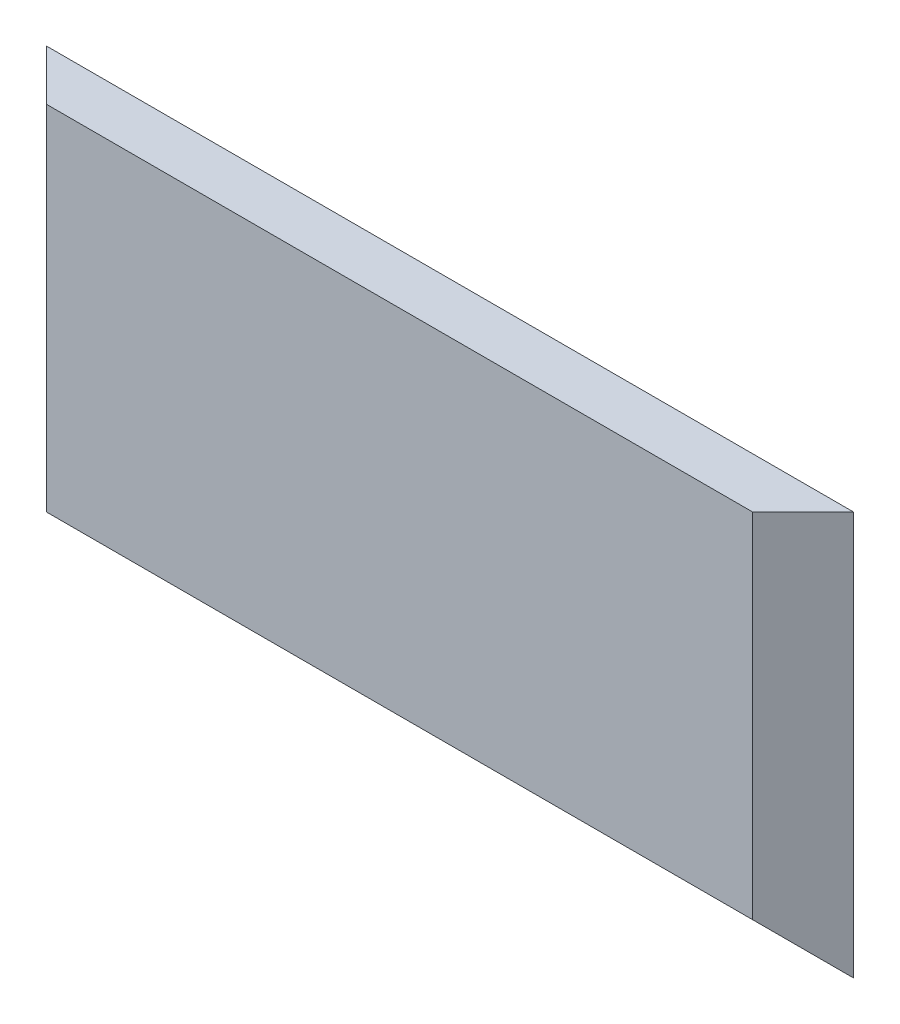
SolidWorks part; units mm, degrees
ref_plane "Front Plane" through (0, 0, 0) normal (0, 0, 1) x (1, 0, 0)
ref_plane "Top Plane" through (0, 0, 0) normal (0, 1, 0) x (1, 0, 0)
ref_plane "Right Plane" through (0, 0, 0) normal (1, 0, 0) x (0, 0, -1)
sketch "Sketch3" plane through (0, 0, 0) normal (0, 1, 0) x (1, 0, 0)
  line L0 (-40, 2.5) -> (-35, -2.5)
  line L1 (-40, 2.5) -> (40, 2.5)
  line L2 (-40, 2.5) -> (-40, -2.5) construction
  line L3 (-35, -2.5) -> (35, -2.5)
  line L4 (40, 2.5) -> (40, -2.5) construction
  line L5 (-40, 2.5) -> (40, -2.5) construction
  line L6 (-40, -2.5) -> (40, 2.5) construction
  line L7 (40, 2.5) -> (35, -2.5)
  point P0 (0, 0)
  dimension "D1" = 5
  dimension "D2" = 80
  dimension "D3" = 45
  dimension "D4" = 45
extrude "Boss-Extrude2" add sketch "Sketch3" along normal blind 40
sketch "Sketch4" plane through (0, 0, 0) normal (1, 0, 0) x (0, 0, -1)
  line L0 (-2.5, 0) -> (2.5, 0) construction
  line L1 (-2.5, 0) -> (2.5, 0)
  line L2 (2.5, 0) -> (-2.5, 5)
  line L3 (-2.5, 40) -> (-2.5, 0) construction
  line L4 (-2.5, 5) -> (-2.5, 0)
  dimension "D1" = 45
extrude "Cut-Extrude1" cut sketch "Sketch4" against normal through all both and the other way through all
